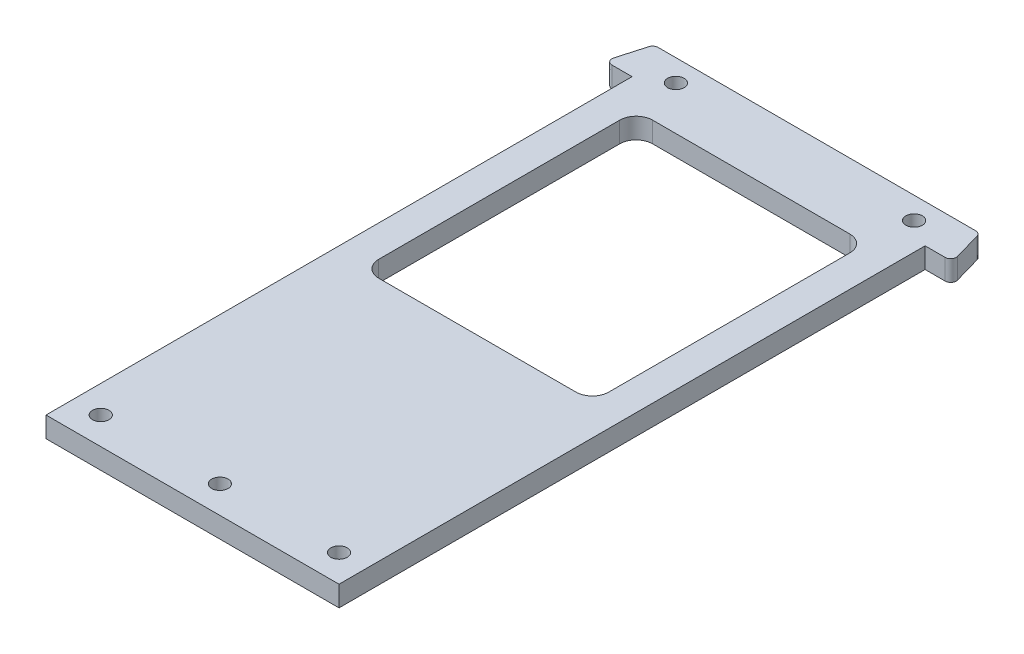
SolidWorks part; units mm, degrees
material "1060 Alloy"
ref_plane "Front Plane" through (0, 0, 0) normal (0, 0, 1) x (1, 0, 0)
ref_plane "Top Plane" through (0, 0, 0) normal (0, 1, 0) x (1, 0, 0)
ref_plane "Right Plane" through (0, 0, 0) normal (1, 0, 0) x (0, 0, -1)
sketch "Sketch1" plane through (0, 0, 0) normal (0, 1, 0) x (1, 0, 0)
  line L1 (0, 0) -> (53.5, 0)
  line L2 (0, 0) -> (0, 114)
  line L3 (0, 114) -> (53.5, 114)
  line L4 (53.5, 0) -> (53.5, 114)
  line L5 (5.75, 102) -> (47.75, 102)
  line L6 (5.75, 102) -> (5.75, 52)
  line L7 (5.75, 52) -> (47.75, 52)
  line L8 (47.75, 102) -> (47.75, 52)
  circle A0 centre (5, 5) radius 1.5
  circle A1 centre (48.5, 5) radius 1.5
  circle A2 centre (26.75, 5) radius 1.5
  circle A3 centre (5, 110) radius 1.5
  circle A4 centre (48.5, 110) radius 1.5
  dimension "D7" = 3
  dimension "D12" = 3
  dimension "D1" = 53.5
  dimension "D2" = 42
  dimension "D3" = 50
  dimension "D4" = 5.75
  dimension "D5" = 12
  dimension "D6" = 52
  dimension "D8" = 5
  dimension "D9" = 5
  dimension "D10" = 5
  dimension "D11" = 26.75
  dimension "D13" = 5
  dimension "D14" = 5
  dimension "D15" = 4
extrude "Boss-Extrude1" add sketch "Sketch1" along normal blind 3.75
fillet "Fillet1" radius 3 4 edges at (47.75, 1.875, -52) (5.75, 1.875, -52) (47.75, 1.875, -102) (5.75, 1.875, -102)
sketch "Sketch2" plane through (0, 3.75, 0) normal (0, 1, 0) x (1, 0, 0)
  line L0 (0, 114) -> (-3, 114)
  line L1 (-3, 114) -> (-5, 107)
  line L2 (-5, 107) -> (0, 107)
  line L3 (0, 114) -> (0, 0) construction
  line L4 (0, 107) -> (0, 114)
  line L5 (53.5, 114) -> (56.5, 114)
  line L6 (56.5, 114) -> (58.5, 107)
  line L7 (58.5, 107) -> (53.5, 107)
  line L8 (53.5, 0) -> (53.5, 114) construction
  line L9 (53.5, 107) -> (53.5, 114)
  dimension "D1" = 7
  dimension "D2" = 5
  dimension "D3" = 3
extrude "Boss-Extrude2" add sketch "Sketch2" against normal up to surface (3.75 mm away) up to face at (5, 0, -108.5)
fillet "Fillet2" radius 1 4 edges at (56.5, 1.875, -114) (58.5, 1.875, -107) (-5, 1.875, -107) (-3, 1.875, -114)
